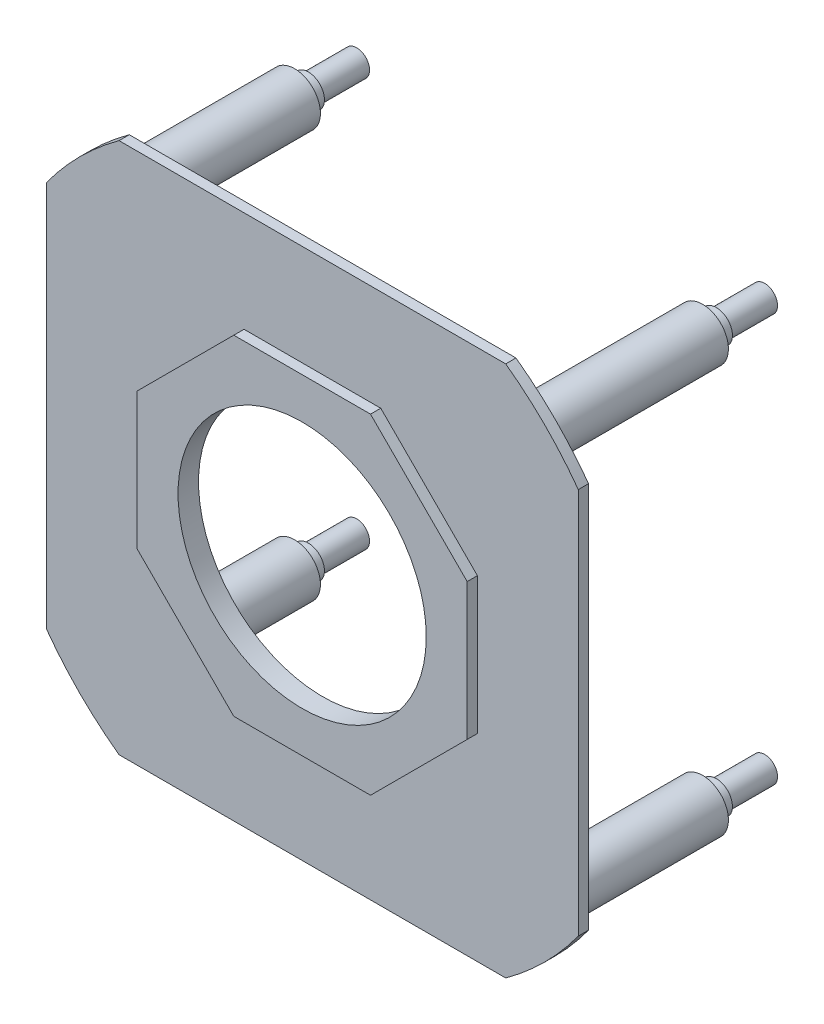
SolidWorks part; units mm, degrees
ref_plane "Front Plane" through (0, 0, 0) normal (0, 0, 1) x (1, 0, 0)
ref_plane "Top Plane" through (0, 0, 0) normal (0, 1, 0) x (1, 0, 0)
ref_plane "Right Plane" through (0, 0, 0) normal (1, 0, 0) x (0, 0, -1)
sketch "Sketch1" plane through (0, 0, 0) normal (0, 0, 1) x (1, 0, 0)
  line L1 (21.2077, 51.2) -> (-21.2077, 51.2)
  line L2 (-21.2077, 51.2) -> (-51.2, 21.2077)
  line L3 (-51.2, 21.2077) -> (-51.2, -21.2077)
  line L4 (-51.2, -21.2077) -> (-21.2077, -51.2)
  line L5 (-21.2077, -51.2) -> (21.2077, -51.2)
  line L6 (21.2077, -51.2) -> (51.2, -21.2077)
  line L7 (51.2, -21.2077) -> (51.2, 21.2077)
  line L8 (51.2, 21.2077) -> (21.2077, 51.2)
  line L9 (101.9739, -101.9739) -> (-101.9739, -101.9739)
  line L10 (101.9739, -101.9739) -> (101.9739, 101.9739)
  line L11 (101.9739, 101.9739) -> (-101.9739, 101.9739)
  line L12 (-101.9739, -101.9739) -> (-101.9739, 101.9739)
  line L13 (101.9739, -101.9739) -> (-101.9739, 101.9739) construction
  line L14 (101.9739, 101.9739) -> (-101.9739, -101.9739) construction
  circle A0 centre (0, 0) radius 38.5
  circle A1 centre (0, 0) radius 51.2 construction
  dimension "D1" = 77
  dimension "D2" = 12.7
extrude "Boss-Extrude1" add sketch "Sketch1" along normal blind 3.175 contours L7 L8 L1 L2 L3 L4 L5 L6 A0 | L12 L9 L10 L11 L8 L7 L6 L5 L4 L3 L2 L1 region at (35.1799, 35.1799, 0) region at (0, -99.0896, 0)
extrude "Boss-Extrude2" add sketch "Sketch1<3>" along normal blind 6.35 contours L7 L8 L1 L2 L3 L4 L5 L6 A0 region at (35.1799, 35.1799, 0)
sketch "Sketch1<3>" plane through (0, 0, 0) normal (0, 0, 1) x (1, 0, 0) same geometry as "Sketch1"
sketch "Sketch2" plane through (0, 0, 0) normal (0, 0, -1) x (-1, 0, 0)
  line L0 (-63.2861, 63.2861) -> (-57.2756, 57.2756) construction
  line L1 (-141688.3503, 141688.3503) -> (176509.7013, -176509.7013) construction
  circle A0 centre (-63.2861, 63.2861) radius 4 construction
  circle A1 centre (-63.2861, 63.2861) radius 4 construction
  arc A2 (-18.9383, 83.1198) -> (-83.1198, 18.9383) centre (0, 0) ccw construction
  circle A3 centre (0, 0) radius 89.5 construction
  circle A4 centre (0, 0) radius 81 construction
  circle A5 centre (-63.2861, 63.2861) radius 8
  point P14 (-60.2809, 60.2809)
  dimension "D1" = 8
  dimension "D2" = 16
extrude "Boss-Extrude3" add sketch "Sketch2" along normal offset from surface (54.6036 mm away) 2
sketch "Sketch3" plane through (0, 0, -54.6036) normal (0, 0, -1) x (-1, 0, 0)
  circle A0 centre (-63.2861, 63.2861) radius 5
  circle A1 centre (-63.2861, 63.2861) radius 8 construction
  circle A2 centre (-63.2861, 63.2861) radius 7.7989 construction
extrude "Boss-Extrude4" add sketch "Sketch3" along normal up to surface (4.25 mm away)
sketch "Sketch4" plane through (0, 0, -58.8536) normal (0, 0, -1) x (-1, 0, 0)
  circle A0 centre (-63.2861, 63.2861) radius 4
  circle A1 centre (-63.2861, 63.2861) radius 8 construction
  dimension "D1" = 8
extrude "Boss-Extrude5" add sketch "Sketch4" along normal blind 15
sketch "Sketch5" plane through (0, 0, 0) normal (0, 0, -1) x (-1, 0, 0)
  line L0 (-141569.8639, -141569.8639) -> (176628.1877, 176628.1877) construction
  line L1 (-141688.3503, 141688.3503) -> (176509.7013, -176509.7013) construction
  circle A0 centre (0, 0) radius 89.5 construction
  point P0 (63.2861, 63.2861)
  point P1 (63.2861, -63.2861)
  point P6 (-63.2861, -63.2861)
  point P7 (0, 0)
  point P10 (0, 0)
  point P11 (0, 0)
pattern_sketch "Sketch-Pattern1" of "Boss-Extrude5", "Boss-Extrude3", "Boss-Extrude4" driven by "Sketch5"
sketch "Sketch6" plane through (0, 0, 0) normal (0, 0, -1) x (-1, 0, 0)
  line L0 (-81, 59.4916) -> (-81, -59.4916) construction
  line L1 (-59.4916, 81) -> (59.4916, 81) construction
  line L2 (81, 59.4916) -> (81, -59.4916) construction
  line L3 (-59.4916, -81) -> (59.4916, -81) construction
  line L4 (-82.5, 59.9812) -> (-82.5, -59.9812)
  line L5 (-59.9812, -82.5) -> (59.9812, -82.5)
  line L6 (82.5, 59.9812) -> (82.5, -59.9812)
  line L7 (-59.9812, 82.5) -> (59.9812, 82.5)
  arc A1 (-59.4916, 81) -> (-81, 59.4916) centre (0, 0) ccw construction
  arc A2 (81, 59.4916) -> (59.4916, 81) centre (0, 0) ccw construction
  arc A3 (59.4916, -81) -> (81, -59.4916) centre (0, 0) ccw construction
  arc A4 (-81, -59.4916) -> (-59.4916, -81) centre (0, 0) ccw construction
  circle A5 centre (0, 0) radius 81 construction
  circle A6 centre (-63.2861, 63.2861) radius 11 construction
  arc A7 (-82.5, -59.9812) -> (-59.9812, -82.5) centre (0, 0) ccw
  arc A8 (59.9812, -82.5) -> (82.5, -59.9812) centre (0, 0) ccw
  arc A9 (82.5, 59.9812) -> (59.9812, 82.5) centre (0, 0) ccw
  arc A10 (-59.9812, 82.5) -> (-82.5, 59.9812) centre (0, 0) ccw
  line M18 (101.9739, -101.9739) -> (101.9739, 101.9739)
  line M19 (101.9739, 101.9739) -> (-101.9739, 101.9739)
  line M20 (-101.9739, 101.9739) -> (-101.9739, -101.9739)
  line M21 (-101.9739, -101.9739) -> (101.9739, -101.9739)
  dimension "D1" = 1.5
extrude "Cut-Extrude1" cut sketch "Sketch6" against normal blind 15 contours A10 L7 A9 L6 A8 L5 A7 L4 M21 M18 M19 M20 region at (0, -99.0896, 0)
